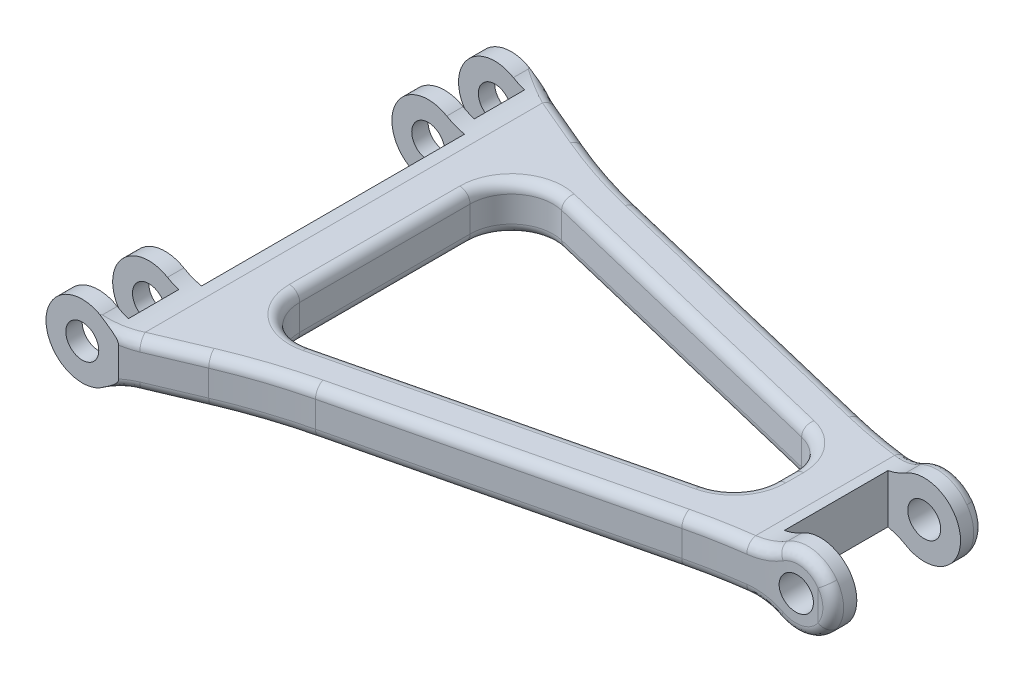
SolidWorks part; units mm, degrees
ref_plane "Front Plane" through (0, 0, 0) normal (0, 0, 1) x (1, 0, 0)
ref_plane "Top Plane" through (0, 0, 0) normal (0, 1, 0) x (1, 0, 0)
ref_plane "Right Plane" through (0, 0, 0) normal (1, 0, 0) x (0, 0, -1)
sketch "Sketch1" plane through (0, 0, 0) normal (0, 1, 0) x (1, 0, 0)
  line L0 (0, -81.0069) -> (0, 81.0069) construction
  line L1 (0, 20.675) -> (-3.5, 20.675)
  line L2 (-3.5, 20.675) -> (-3.5, 12.675) construction
  line L3 (-3.5, 12.675) -> (3.5, 12.675)
  line L4 (3.5, 12.675) -> (3.5, -12.675)
  line L5 (3.5, -12.675) -> (-3.5, -12.675)
  line L6 (-3.5, -12.675) -> (-3.5, -20.675) construction
  line L7 (-3.5, -20.675) -> (0, -20.675)
  line L8 (0, -20.675) -> (3.5, -20.675)
  line L9 (3.5, -20.675) -> (59, -7.2719) construction
  line L10 (59, 7.2719) -> (59, 5)
  line L11 (52, 5) -> (52, -5)
  line L12 (52, -5) -> (59, -5)
  line L13 (59, -5) -> (59, -7.2719)
  line L14 (59, 7.2719) -> (3.5, 20.675) construction
  line L15 (3.5, 20.675) -> (0, 20.675)
  line L16 (59, 5) -> (52, 5)
  line L17 (3.5, 50.1487) -> (3.5, -45.1899) construction
  line L18 (8.5, 13.295) -> (47, 3.9974)
  line L19 (47, 3.9974) -> (47, -3.9974)
  line L20 (47, -3.9974) -> (8.5, -13.295)
  line L21 (8.5, -13.295) -> (8.5, 13.295)
  line L22 (-3.5, -12.675) -> (-3.5, -14.25)
  line L23 (-3.5, -14.25) -> (2.8653, -14.25)
  line L24 (2.8653, -14.25) -> (2.8653, -19.1)
  line L25 (2.8653, -19.1) -> (-3.5, -19.1)
  line L26 (-3.5, -19.1) -> (-3.5, -20.675)
  line L27 (-3.5, 12.675) -> (-3.5, 14.25)
  line L28 (-3.5, 14.25) -> (2.8653, 14.25)
  line L29 (2.8653, 14.25) -> (2.8653, 19.1)
  line L30 (2.8653, 19.1) -> (-3.5, 19.1)
  line L31 (-3.5, 19.1) -> (-3.5, 20.675)
  line L32 (0, 0) -> (3.5, 0) construction
  line L33 (3.5, 0) -> (8.5, 0) construction
  line L34 (8.5, 0) -> (47, 0) construction
  line L35 (47, 0) -> (52, 0) construction
  line L36 (3.5, -20.675) -> (13.3724, -16.4995)
  line L37 (13.3724, -16.4995) -> (51.5825, -7.2719)
  line L38 (51.5825, -7.2719) -> (59, -7.2719)
  line L39 (3.5, 20.675) -> (13.3724, 16.4995)
  line L40 (13.3724, 16.4995) -> (51.5825, 7.2719)
  line L41 (51.5825, 7.2719) -> (59, 7.2719)
  line L42 (13.3724, 16.4995) -> (13.3724, -16.4995) construction
  line L43 (51.5825, 7.2719) -> (51.5825, -7.2719) construction
  dimension "D1" = 6
  dimension "D2" = 6
  dimension "D3" = 8
  dimension "D4" = 5
  dimension "D5" = 5
  dimension "D6" = 10
  dimension "D7" = 7
  dimension "D8" = 28.5
  dimension "D9" = 38.2
  dimension "D10" = 59
  dimension "D11" = 7
extrude "Boss-Extrude1" add sketch "Sketch1" along normal blind 7
sketch "Sketch2" plane through (0, 0, 0) normal (0, 0, 1) x (1, 0, 0)
  line L0 (-3.5, 7) -> (3.5, 7) construction
  line L1 (4.5483, 5.75) -> (4.5483, 1.25) construction
  line L2 (1.7887, 6.5084) -> (1.7887, 0.4916) construction
  line L3 (6.3383, 5.75) -> (1.7998, 5.75) construction
  line L4 (-3.5, 7) -> (-3.5, 0) construction
  line L5 (4.5483, 1.25) -> (50.9517, 1.25)
  line L6 (4.5483, 5.75) -> (50.9517, 5.75)
  line L7 (50.9517, 5.75) -> (50.9517, 1.25) construction
  line L8 (53.7113, 0.4916) -> (53.7113, 6.5084) construction
  line L10 (59, 0) -> (3.5, 0) construction
  line L12 (55.5, 7) -> (55.5, 0) construction
  line L15 (51.5825, 7) -> (59, 7) construction
  line L16 (59, 7) -> (59, 0) construction
  circle A0 centre (0, 3.5) radius 1.5875
  arc A1 (0, 0) -> (0, 7) centre (0, 3.5) cw
  arc A2 (0, 0) -> (1.7887, 0.4916) centre (0, 3.5) ccw
  arc A3 (0, 7) -> (1.7887, 6.5084) centre (0, 3.5) cw
  arc A4 (1.7887, 6.5084) -> (4.5483, 5.75) centre (4.5483, 11.1497) ccw
  arc A5 (1.7887, 0.4916) -> (4.5483, 1.25) centre (4.5483, -4.1497) cw
  arc A6 (55.5, 7) -> (55.5, 0) centre (55.5, 3.5) cw
  arc A7 (55.5, 7) -> (53.7113, 6.5084) centre (55.5, 3.5) ccw
  arc A8 (55.5, 0) -> (53.7113, 0.4916) centre (55.5, 3.5) cw
  arc A9 (50.9517, 5.75) -> (53.7113, 6.5084) centre (50.9517, 11.1497) ccw
  arc A10 (50.9517, 1.25) -> (53.7113, 0.4916) centre (50.9517, -4.1497) cw
  circle A11 centre (55.5, 3.5) radius 1.5875
  dimension "D1" = 3.175
  dimension "D3" = 3.175
  dimension "D2" = 4.5
extrude "Cut-Extrude1" cut sketch "Sketch2" against normal through all and the other way through all flip side to cut
fillet "Fillet1" radius 50 4 edges at (51.5825, 3.5, 7.2719) (13.3724, 3.5, 16.4995) (13.3724, 3.5, -16.4995) (51.5825, 3.5, -7.2719)
fillet "Fillet2" radius 4 4 edges at (8.5, 3.5, 13.295) (47, 3.5, -3.9974) (8.5, 3.5, -13.295) (47, 3.5, 3.9974)
fillet "Fillet3" radius 1 46 edges at (4.0216, 1.2243, -20.4544) (52.7328, 0.9478, -7.503) (59, 3.5, -7.2719) (52.0216, 5.8571, -7.5767) (4.0216, 5.7757, -20.4544) (4.0216, 5.7757, 20.4544) (4.0216, 1.2243, 20.4544) (52.0216, 1.1429, 7.5767) (59, 3.5, 7.2719) (52.7328, 6.0522, 7.503) (48.3617, 1.25, 8.1204) (48.3617, 1.25, -8.1204) (31.5717, 1.25, -12.1044) (13.4246, 1.25, -16.658) (7.0776, 1.25, -19.1619) (7.0776, 1.25, 19.1619) (13.4246, 1.25, 16.658) (31.5717, 1.25, 12.1044) (10.0257, 1.25, 11.357) (8.5, 1.25, 0) (10.0257, 1.25, -11.357) (28.689, 1.25, -8.4194) (46.1429, 1.25, -3.3226) (47, 1.25, 0) (46.1429, 1.25, 3.3226) (28.689, 1.25, 8.4194) (7.0776, 5.75, -19.1619) (13.4246, 5.75, -16.658) (31.5717, 5.75, -12.1044) (48.3617, 5.75, -8.1204) (48.3617, 5.75, 8.1204) (31.5717, 5.75, 12.1044) (13.4246, 5.75, 16.658) (7.0776, 5.75, 19.1619) (10.0257, 5.75, -11.357) (8.5, 5.75, 0) (10.0257, 5.75, 11.357) (28.689, 5.75, 8.4194) (46.1429, 5.75, 3.3226) (47, 5.75, 0) (46.1429, 5.75, -3.3226) (28.689, 5.75, -8.4194) (55.9843, 0.0337, -7.2959) (55.3143, 6.9951, -7.3212) (55.3143, 0.0049, 7.3212) (55.9843, 6.9663, 7.2959)
